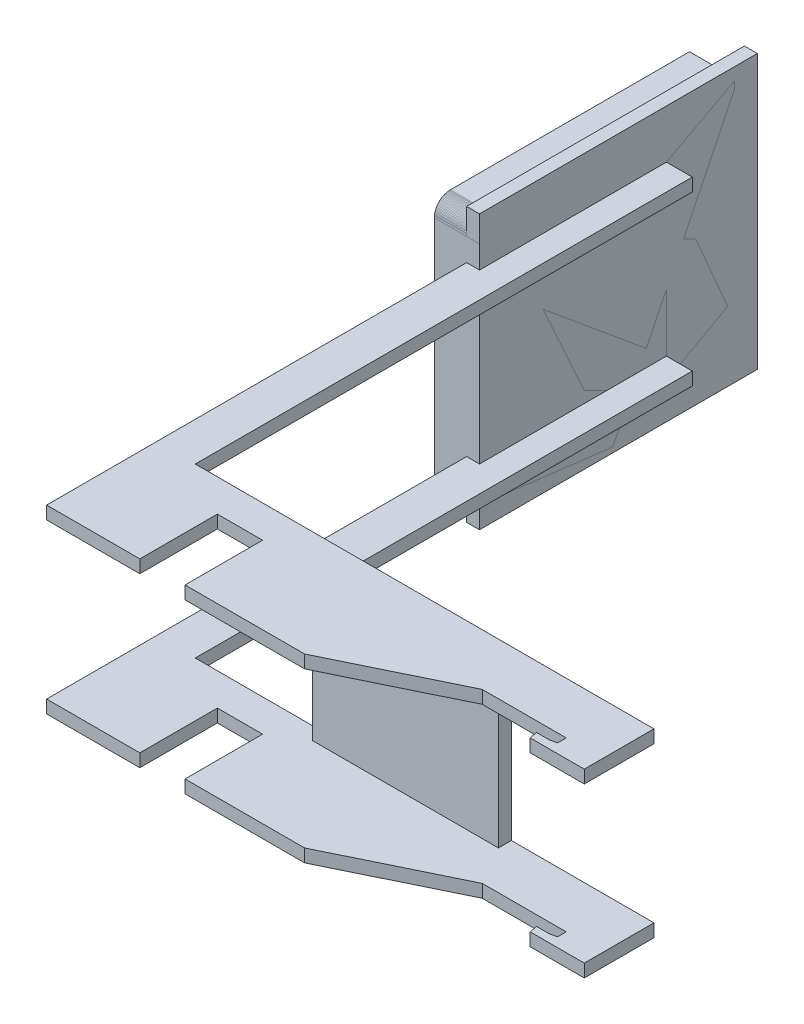
SolidWorks part; units mm, degrees
ref_plane "Front" through (0, 0, 0) normal (0, 0, 1) x (1, 0, 0)
ref_plane "Top" through (0, 0, 0) normal (0, 1, 0) x (1, 0, 0)
ref_plane "Right" through (0, 0, 0) normal (1, 0, 0) x (0, 0, -1)
sketch "Sketch1" plane through (0, 0, 0) normal (0, 1, 0) x (1, 0, 0)
  line L1 (0, 0) -> (75, 0)
  line L2 (0, 0) -> (0, 17)
  line L3 (0, 17) -> (75, 17)
  line L4 (75, 0) -> (75, 17)
  dimension "D1" = 75
  dimension "D2" = 17
extrude "Boss-Extrude1" add sketch "Sketch1" along normal blind 2
sketch "Sketch2" plane through (0, 2, 0) normal (0, 1, 0) x (1, 0, 0)
  line L0 (0, 0) -> (75, 0) construction
  line L1 (12.4214, 0) -> (19.4214, 0)
  line L2 (12.4214, 0) -> (12.4214, 12)
  line L3 (12.4214, 12) -> (19.4214, 12)
  line L4 (19.4214, 0) -> (19.4214, 12)
  line L7 (69.4214, 9) -> (69.4214, 8.0081)
  line L8 (56.4214, 9) -> (69.4214, 9)
  line L9 (56.4214, 9) -> (56.4214, 0)
  line L10 (56.4214, 0) -> (69.4214, 0)
  line L11 (69.4214, 8.0081) -> (66.3916, 7.4309)
  line L12 (66.3916, 7.4309) -> (66.6241, 6.2109)
  line L13 (66.6241, 6.2109) -> (75, 6.2109)
  line L14 (75, 0) -> (75, 17) construction
  line L15 (75, 6.2109) -> (75, 0)
  line L16 (75, 0) -> (69.4214, 0)
  dimension "D1" = 7
  dimension "D2" = 12
  dimension "D5" = 9
extrude "Cut-Extrude1" cut sketch "Sketch2" against normal through all
ref_plane "Plane1" through (0, 14, 0) normal (0, 1, 0) x (1, 0, 0)
mirror "Mirror7" about plane through (0, 14, 0) normal (0, 1, 0) of bodies 102
ref_plane "Plane2" through (0, 0, -17) normal (0, 0, -1) x (-1, 0, 0)
sketch "Sketch4" plane through (0, 0, -17) normal (0, 0, -1) x (-1, 0, 0)
  line L0 (-75, 28) -> (0, 28) construction
  line L1 (-52.9254, 28) -> (-24.1658, 28)
  line L2 (-52.9254, 28) -> (-52.9254, 0)
  line L3 (-52.9254, 0) -> (-24.1658, 0)
  line L4 (-24.1658, 28) -> (-24.1658, 0)
  line L5 (-75, 0) -> (0, 0) construction
extrude "Boss-Extrude4" add sketch "Sketch4" against normal blind 2 contours L4 L3 L2 L1
ref_plane "Plane3" through (0, 0, 0) normal (-1, 0, 0) x (0, 0, 1)
sketch "Sketch5" plane through (0, 0, 0) normal (0, -1, 0) x (1, 0, 0)
  line L0 (56.4214, 0) -> (37.9214, 0)
  line L1 (19.4214, 0) -> (56.4214, 0) construction
  line L2 (37.9214, 0) -> (56.4214, -9)
  line L3 (56.4214, -9) -> (56.4214, 0)
extrude "Cut-Extrude2" cut sketch "Sketch5" against normal through all
sketch "Sketch6" plane through (0, 0, 0) normal (-1, 0, 0) x (0, 0, 1)
  line L0 (-8.5, 0) -> (-8.5, 28) construction
  line L1 (-17, 0) -> (0, 0) construction
  line L2 (-17, 28) -> (0, 28) construction
  line L3 (0, 0) -> (0, 28) construction
  line L4 (-17, 2) -> (0, 2) construction
  line L5 (0, 0) -> (-108, 0)
  line L6 (0, 0) -> (0, 2)
  line L7 (0, 2) -> (-108, 2)
  line L8 (-65, 14.3589) -> (-108, 14.3589) construction
  line L9 (-108, -6.8161) -> (-65, -6.8161)
  line L10 (-108, -6.8161) -> (-108, 35.5339)
  line L11 (-108, 35.5339) -> (-65, 35.5339)
  line L12 (-65, -6.8161) -> (-65, 35.5339)
  line L13 (-108, 14.3589) -> (-64.0669, 14.3589) construction
  line L14 (-108, 0) -> (-108, 2)
  line L15 (0, 28) -> (-108, 28)
  line L16 (0, 28) -> (0, 26)
  line L17 (0, 26) -> (-108, 26)
  line L18 (-108, 28) -> (-108, 26)
  line L19 (-17, 26) -> (0, 26) construction
  dimension "D2" = 43
  dimension "D3" = 42.35
extrude "Boss-Extrude5" add sketch "Sketch6" along normal blind 2 contours L12 L17 L10 L7 | L9 L12 L5 L10 | L15 L12 L11 L10 | L5 L14 L7 L6 | L17 L18 L15 L16 region at (0, -3.408, -86.5) region at (0, 14, -86.5) region at (0, 31.767, -86.5)
sketch "Sketch7" plane through (0, 0, 0) normal (1, 0, 0) x (0, 0, -1)
  line L0 (17, 26) -> (65, 26) construction
  line L1 (17, 28) -> (93.9272, 28)
  line L2 (17, 28) -> (17, 26)
  line L3 (17, 26) -> (93.9272, 26)
  line L4 (93.9272, 28) -> (93.9272, 26)
  line L5 (93.9272, 0) -> (17, 0)
  line L6 (93.9272, 0) -> (93.9272, 2)
  line L7 (93.9272, 2) -> (17, 2)
  line L8 (17, 0) -> (17, 2)
  line L9 (93.9272, 26) -> (93.9272, 2) construction
extrude "Boss-Extrude6" add sketch "Sketch7" along normal blind 4
sketch "Sketch8" plane through (-2, 0, 0) normal (-1, 0, 0) x (0, 0, 1)
  line L0 (-67.5, -3.515) -> (-67.5, 31.515) construction
  line L1 (-65, 2) -> (-65, 26) construction
  line L2 (-65, 14) -> (-67.5, 14) construction
  line L3 (-65, 28) -> (-65, 35.5339) construction
  line L4 (-65, 31.515) -> (-65, 39.0874) construction
  circle A0 centre (-67.5, 31.515) radius 2.5
  circle A1 centre (-67.5, 31.515) radius 0.75
  circle A2 centre (-67.5, -3.515) radius 0.75
  circle A3 centre (-67.5, -3.515) radius 2.5
  circle A4 centre (-104.5, 30.085) radius 0.75
  circle A5 centre (-104.5, 30.085) radius 2.5
  dimension "D5" = 35.03
  dimension "D1" = 1.5
  dimension "D2" = 1.75
  dimension "D3" = 1.5
  dimension "D4" = 1.75
  dimension "D6" = 1.5
  dimension "D7" = 1.75
  dimension "D10" = 0
  dimension "D8" = 37
  dimension "D9" = 1.43
extrude "Boss-Extrude8" add sketch "Sketch8" along normal blind 5
sketch "Sketch15" plane through (0, 28, 0) normal (0, 1, 0) x (1, 0, 0)
  line L0 (66.3916, 7.4309) -> (68.3456, 7.4309)
  line L2 (69.4214, 8.0081) -> (69.4214, 6.8363) construction
  line L3 (68.3456, 7.4309) -> (69.4214, 7.6658)
  line L4 (69.4214, 7.6658) -> (69.4214, 8.0081)
  line L5 (69.4214, 8.0081) -> (66.3916, 7.4309)
extrude "Cut-Extrude3" cut sketch "Sketch15" against normal through all
ref_plane "Plane4" through (-7, 0, 0) normal (-1, 0, 0) x (0, 0, 1)
sketch "Sketch16" plane through (-7, 0, 0) normal (-1, 0, 0) x (0, 0, 1)
  line L0 (-65, 31.515) -> (-65, -3.515)
  line L1 (-67.5, 34.015) -> (-104.5, 34.015)
  line L2 (-104.5, 34.015) -> (-104.5, 32.585)
  line L3 (-67.5, -6.015) -> (-85.6265, -6.015)
  line L4 (-107, 30.085) -> (-107, 5.9594)
  line L5 (-107, 5.9594) -> (-85.6265, -6.015)
  circle A0 centre (-67.5, -3.515) radius 2.5
  circle A1 centre (-67.5, 31.515) radius 2.5
  circle A2 centre (-104.5, 30.085) radius 2.5
extrude "Boss-Extrude9" add sketch "Sketch16" against normal up to vertex (7 mm away) separate body contours A2 L4 L5 L3 A0 L0 A1 L1 L2 | A2 | A1 | A0 region at (-7, 31.515, -67.5) region at (-7, 15.1041, -85.021) region at (-7, -3.515, -67.5) region at (-7, 30.085, -104.5) up to point (0, 35.5339, -108)
